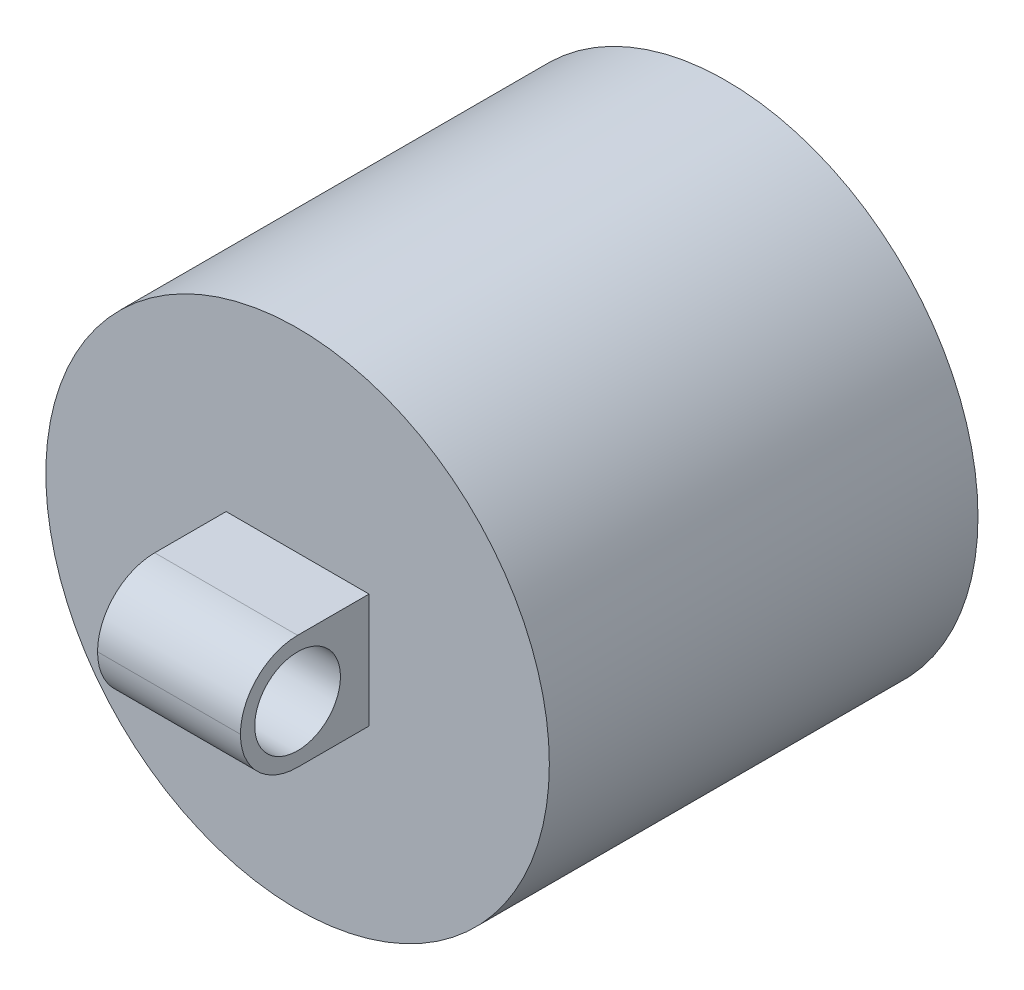
SolidWorks part; units mm, degrees
ref_plane "Front Plane" through (0, 0, 0) normal (0, 0, 1) x (1, 0, 0)
ref_plane "Top Plane" through (0, 0, 0) normal (0, 1, 0) x (1, 0, 0)
ref_plane "Right Plane" through (0, 0, 0) normal (1, 0, 0) x (0, 0, -1)
sketch "Sketch1" plane through (0, 0, 0) normal (0, 0, 1) x (1, 0, 0)
  circle A0 centre (0, 0) radius 8.81
  dimension "D1" = 8.81
extrude "Boss-Extrude1" add sketch "Sketch1" along normal blind 15
sketch "Sketch2" plane through (0, 0, 15) normal (0, 0, 1) x (1, 0, 0)
  line L1 (-2.5, -2) -> (2.5, -2)
  line L2 (-2.5, -2) -> (-2.5, 2)
  line L3 (-2.5, 2) -> (2.5, 2)
  line L4 (2.5, -2) -> (2.5, 2)
  line L5 (-2.5, -2) -> (2.5, 2) construction
  line L6 (-2.5, 2) -> (2.5, -2) construction
  point P0 (0, 0)
  dimension "D1" = 5
  dimension "D2" = 4
extrude "Boss-Extrude2" add sketch "Sketch2" along normal blind 4.5 contours L2 L1 L4 L3
fillet "Fillet7" radius 2 2 edges at (0, 2, 19.5) (0, -2, 19.5)
sketch "Sketch3" plane through (2.5, 0, 0) normal (1, 0, 0) x (0, 0, -1)
  line L0 (-15, -2) -> (-15, 2) construction
  circle A0 centre (-17.5, 0) radius 1.5
  dimension "D1" = 2.5
  dimension "D2" = 3
  dimension "D3" = 2
extrude "Cut-Extrude1" cut sketch "Sketch3" against normal through all
